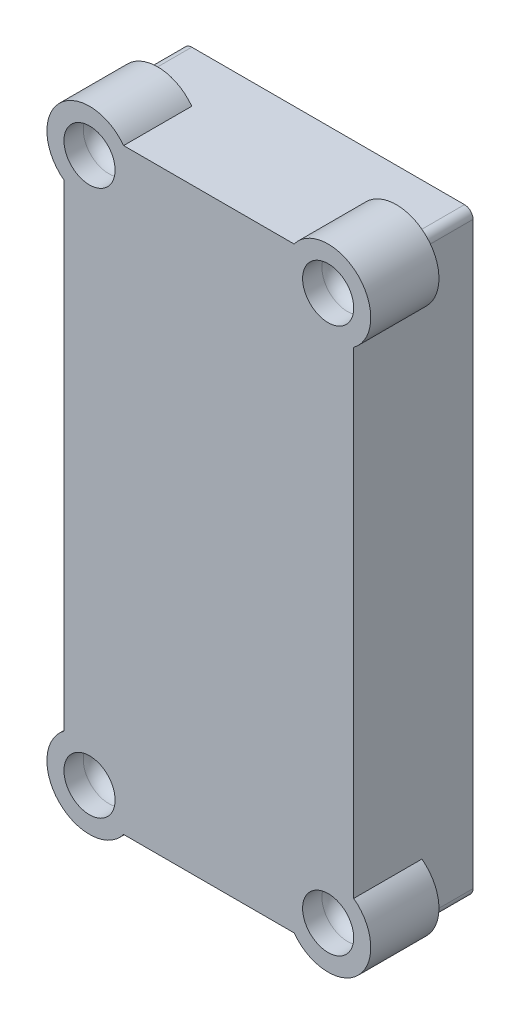
SolidWorks part; units mm, degrees
ref_plane "Front Plane" through (0, 0, 0) normal (0, 0, 1) x (1, 0, 0)
ref_plane "Top Plane" through (0, 0, 0) normal (0, 1, 0) x (1, 0, 0)
ref_plane "Right Plane" through (0, 0, 0) normal (1, 0, 0) x (0, 0, -1)
sketch "Sketch1" plane through (0, 0, 0) normal (0, 0, 1) x (1, 0, 0)
  line L5 (0, 0) -> (34, 0)
  line L6 (0, 0) -> (0, 70)
  line L7 (0, 70) -> (34, 70)
  line L8 (34, 0) -> (34, 70)
  dimension "D1" = 34
  dimension "D2" = 70
extrude "Boss-Extrude1" add sketch "Sketch1" along normal blind 14
sketch "Sketch2" plane through (0, 0, 0) normal (0, 0, -1) x (-1, 0, 0)
  line L0 (-34, 70) -> (0, 70) construction
  line L1 (-32, 68) -> (-2, 68)
  line L2 (-32, 68) -> (-32, 2)
  line L3 (-32, 2) -> (-2, 2)
  line L4 (-2, 68) -> (-2, 2)
  line L5 (0, 70) -> (0, 0) construction
  line L6 (-34, 0) -> (-34, 70) construction
  point P4 (-17, 68)
  point P7 (-17, 70)
  point P8 (-2, 35)
  point P11 (0, 35)
  dimension "D1" = 2
  dimension "D2" = 2
extrude "Cut-Extrude1" cut sketch "Sketch2" against normal offset from surface (12 mm away) 2 up to face at (17, 35, 14)
sketch "Sketch3" plane through (0, 0, 0) normal (0, 0, -1) x (-1, 0, 0)
  line L0 (-34, 70) -> (0, 70) construction
  line L1 (-34, 0) -> (-34, 70) construction
  line L2 (0, 70) -> (0, 0) construction
  line L3 (0, 0) -> (-34, 0) construction
  circle A0 centre (-31, 67) radius 3
  circle A1 centre (-3, 67) radius 3
  circle A2 centre (-3, 3) radius 3
  circle A3 centre (-31, 3) radius 3
  dimension "D1" = 6
  dimension "D2" = 6
  dimension "D3" = 6
  dimension "D4" = 6
extrude "Boss-Extrude2" add sketch "Sketch3" against normal up to surface (12 mm away) up to face at (17, 35, 12)
sketch "Sketch4" plane through (0, 0, 0) normal (0, 0, -1) x (-1, 0, 0)
  circle A0 centre (-3, 67) radius 2
  circle A1 centre (-31, 67) radius 2
  circle A2 centre (-3, 3) radius 2
  circle A3 centre (-31, 3) radius 2
  dimension "D1" = 4
  dimension "D2" = 4
  dimension "D3" = 4
  dimension "D4" = 4
extrude "Cut-Extrude2" cut sketch "Sketch4" against normal through all
sketch "Sketch6" plane through (0, 0, 0) normal (0, -1, 0) x (1, 0, 0)
  line L0 (9.5, 0) -> (24.5, 0) construction
  line L1 (0, 0) -> (34, 0) construction
  circle A0 centre (9.5, 0) radius 2.5
  circle A1 centre (24.5, 0) radius 2
  point P5 (17, 0)
  point P6 (17, 0)
  dimension "D1" = 5
  dimension "D2" = 4
  dimension "D3" = 15
extrude "Cut-Extrude4" cut sketch "Sketch6" against normal up to next
fillet "Fillet1" radius 1 4 edges at (34, 70, 7) (0, 70, 7) (0, 0, 7) (34, 0, 7)
sketch "Sketch7" plane through (0, 0, 14) normal (0, 0, 1) x (1, 0, 0)
  circle A0 centre (31, 67) radius 3
  circle A1 centre (3, 67) radius 3
  circle A2 centre (3, 3) radius 3
  circle A3 centre (31, 3) radius 3
  circle A4 centre (31, 67) radius 5
  circle A5 centre (3, 67) radius 5
  circle A6 centre (31, 3) radius 5
  circle A7 centre (3, 3) radius 5
  dimension "D1" = 6
  dimension "D2" = 6
  dimension "D3" = 6
  dimension "D4" = 6
  dimension "D5" = 10
  dimension "D6" = 10
  dimension "D7" = 10
  dimension "D8" = 10
extrude "Boss-Extrude3" add sketch "Sketch7" against normal offset from surface (8 mm away) 6 up to face at (17.25, 1, 0)
sketch "Sketch8" plane through (0, 0, 14) normal (0, 0, 1) x (1, 0, 0)
  circle A0 centre (3, 3) radius 3
  circle A1 centre (31, 3) radius 3
  circle A2 centre (31, 67) radius 3
  circle A4 centre (3, 67) radius 3
  dimension "D1" = 6
  dimension "D2" = 6
  dimension "D3" = 6
  dimension "D4" = 6
extrude "Cut-Extrude7" cut sketch "Sketch8" against normal offset from surface (4 mm away) 10 up to face at (17.25, 1, 0)
fillet "Fillet2" radius 2 4 edges at (28, 3, 10) (28, 67, 10) (0, 67, 10) (0, 3, 10)
